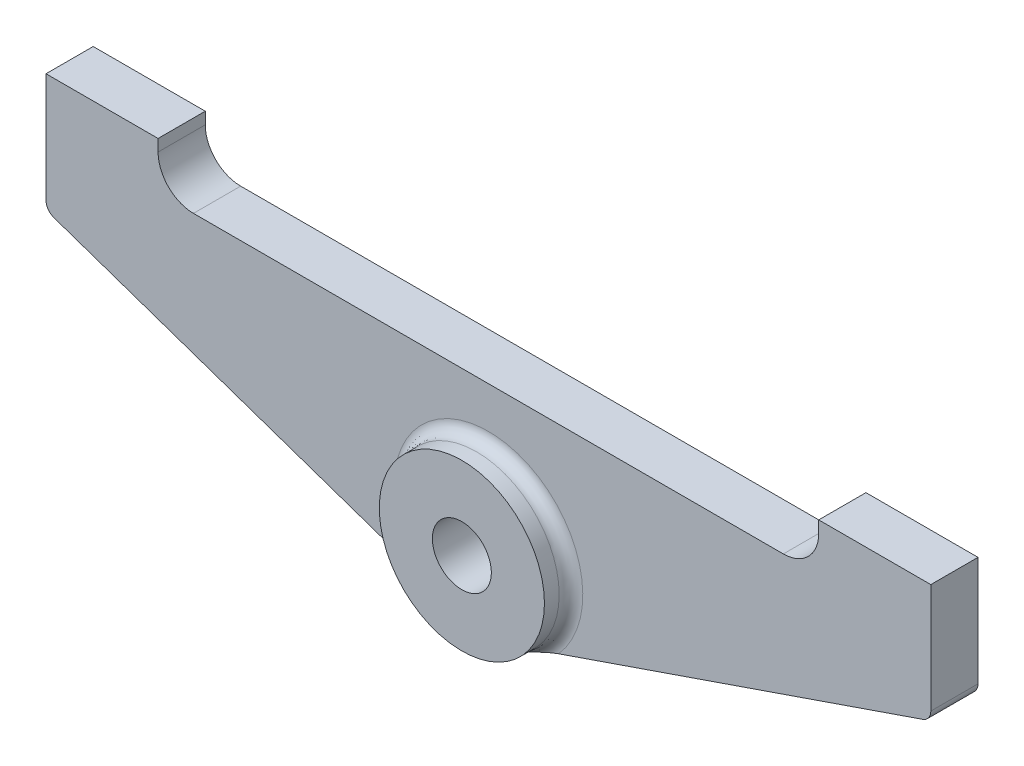
SolidWorks part; units mm, degrees
ref_plane "Front Plane" through (0, 0, 0) normal (0, 0, 1) x (1, 0, 0)
ref_plane "Top Plane" through (0, 0, 0) normal (0, 1, 0) x (1, 0, 0)
ref_plane "Right Plane" through (0, 0, 0) normal (1, 0, 0) x (0, 0, -1)
sketch "Sketch1" plane through (0, 0, 0) normal (0, 0, 1) x (1, 0, 0)
  line L0 (22.7747, -66.1915) -> (375, 55)
  line L1 (375, 55) -> (375, 155)
  line L2 (375, 155) -> (280, 155)
  line L3 (280, 155) -> (280, 115)
  line L4 (280, 115) -> (-280, 115)
  line L5 (0, 132.2177) -> (0, -97.5318) construction
  line L6 (-280, 155) -> (-280, 115)
  line L7 (-375, 155) -> (-280, 155)
  line L8 (-375, 55) -> (-375, 155)
  line L9 (-22.7747, -66.1915) -> (-375, 55)
  circle A0 centre (0, 0) radius 70
  circle A1 centre (0, 0) radius 25
  point P12 (0, -70)
  point P13 (0, 115)
  point P15 (0, 115)
  dimension "D1" = 50
  dimension "D2" = 140
  dimension "D3" = 95
  dimension "D4" = 40
  dimension "D5" = 100
  dimension "D6" = 225
  dimension "D7" = 375
extrude "Boss-Extrude1" add sketch "Sketch1" along normal mid plane 40 contours L4 L5 A0 L0 L1 L2 L3 | L5 L4 L6 L7 L8 L9 A0 region at (193.1147, 63.5522, 0) region at (-193.1147, 63.5522, 0)
extrude "Boss-Extrude2" add sketch "Sketch1<3>" along normal mid plane 85 contours L5 A0 A1 | A0 L5 A1 region at (32.5011, 0, 0) region at (-32.5011, 0, 0)
sketch "Sketch1<3>" plane through (0, 0, 0) normal (0, 0, 1) x (1, 0, 0) same geometry as "Sketch1"
fillet "Fillet1" radius 10 4 edges at (-375, 55, 0) (375, 55, 0) (0, 70, 20) (0, 70, -20)
fillet "Fillet2" radius 30 2 edges at (280, 115, 0) (-280, 115, 0)
